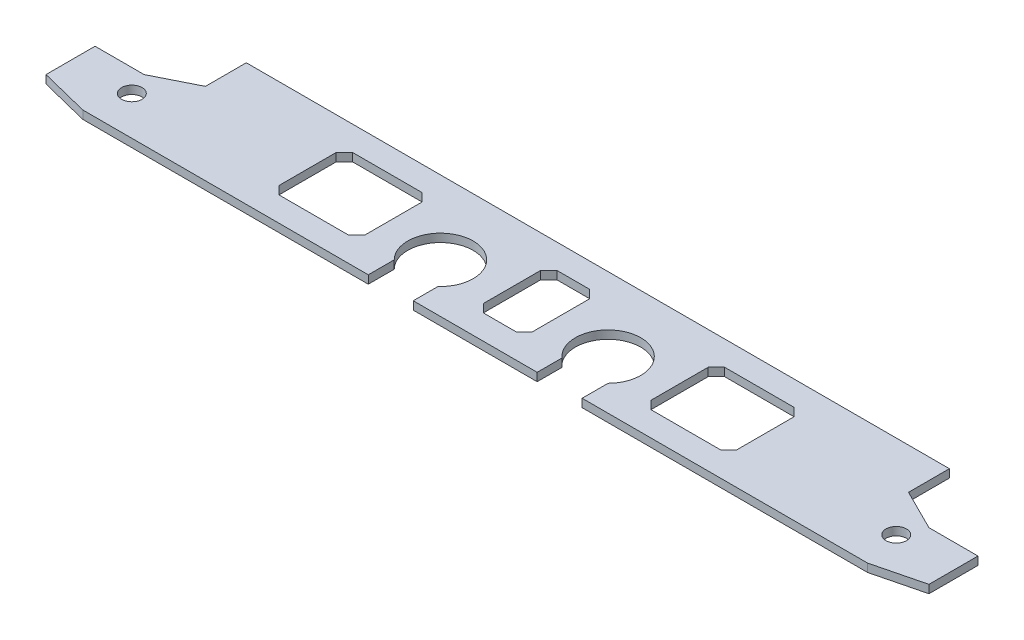
SolidWorks part; units mm, degrees
material "Thornel Mat VMA"
ref_plane "Alzado" through (0, 0, 0) normal (0, 0, 1) x (1, 0, 0)
ref_plane "Planta" through (0, 0, 0) normal (0, 1, 0) x (1, 0, 0)
ref_plane "Vista lateral" through (0, 0, 0) normal (1, 0, 0) x (0, 0, -1)
sketch "Croquis1" plane through (0, 0, 0) normal (0, 1, 0) x (1, 0, 0)
  line L1 (-43, 7.5) -> (43, 7.5)
  line L2 (-43, 7.5) -> (-43, -7.5)
  line L3 (-43, -7.5) -> (43, -7.5)
  line L4 (43, 7.5) -> (43, -7.5)
  line L5 (-43, 7.5) -> (43, -7.5) construction
  line L6 (-43, -7.5) -> (43, 7.5) construction
  point P0 (0, 0)
  dimension "D1" = 15
  dimension "D2" = 86
extrude "Saliente-Extruir1" add sketch "Croquis1" along normal blind 1
sketch "Croquis2" plane through (0, 1, 0) normal (0, 1, 0) x (1, 0, 0)
  line L0 (0, 7.5) -> (0, -7.5) construction
  line L1 (-3, 4.5) -> (3, 4.5)
  line L2 (-3, 4.5) -> (-3, -4.5)
  line L3 (-3, -4.5) -> (3, -4.5)
  line L4 (3, 4.5) -> (3, -4.5)
  line L5 (-3, 4.5) -> (3, -4.5) construction
  line L6 (-3, -4.5) -> (3, 4.5) construction
  line L7 (-43, -7.5) -> (43, -7.5) construction
  line L8 (43, -7.5) -> (43, 7.5) construction
  line L9 (17.5, 4.5) -> (28, 4.5)
  line L10 (17.5, 4.5) -> (17.5, -4.5)
  line L11 (17.5, -4.5) -> (28, -4.5)
  line L12 (28, 4.5) -> (28, -4.5)
  line L13 (17.5, 4.5) -> (28, -4.5) construction
  line L14 (17.5, -4.5) -> (28, 4.5) construction
  line L15 (-17.5, -4.5) -> (-28, -4.5)
  line L16 (-28, 4.5) -> (-28, -4.5)
  line L17 (-17.5, 4.5) -> (-28, 4.5)
  line L18 (-17.5, 4.5) -> (-17.5, -4.5)
  point P0 (0, 0)
  point P5 (22.75, 0)
  point P11 (0, 0)
  dimension "D1" = 9
  dimension "D2" = 6
  dimension "D3" = 9
  dimension "D4" = 10.5
  dimension "D5" = 15
extrude "Cortar-Extruir1" cut sketch "Croquis2" against normal blind 1
chamfer "Chaflán1" distance 1 12 edges at (17.5, 0.5, -4.5) (28, 0.5, -4.5) (3, 0.5, -4.5) (-3, 0.5, -4.5) (-3, 0.5, 4.5) (17.5, 0.5, 4.5) (28, 0.5, 4.5) (3, 0.5, 4.5) (-17.5, 0.5, 4.5) (-28, 0.5, 4.5) (-17.5, 0.5, -4.5) (-28, 0.5, -4.5)
sketch "Croquis3" plane through (0, 1, 0) normal (0, 1, 0) x (1, 0, 0)
  line L0 (0, 0) -> (0, -7.5) construction
  line L1 (-43, -7.5) -> (43, -7.5) construction
  line L2 (6.25, -1.5) -> (6.25, 2.5) construction
  line L3 (6.25, 2.5) -> (10.25, 2.5) construction
  line L4 (43, 7.5) -> (-43, 7.5) construction
  line L5 (3, -1.5) -> (17.5, -1.5) construction
  line L6 (3, -3.5) -> (3, 3.5) construction
  line L7 (17.5, 3.5) -> (17.5, -3.5) construction
  line L8 (-13.0785, -7.5) -> (-7.5785, -7.5)
  line L9 (7.5785, -7.5) -> (7.5785, -4.4771)
  line L11 (13.0785, -4.3283) -> (13.0785, -7.5)
  line L12 (13.0785, -7.5) -> (7.5785, -7.5)
  line L13 (-13.0785, -4.3283) -> (-13.0785, -7.5)
  line L14 (-7.5785, -7.5) -> (-7.5785, -4.4771)
  arc A0 (13.0785, -4.3283) -> (7.5785, -4.4771) centre (10.25, -1.5) ccw
  arc A1 (-13.0785, -4.3283) -> (-7.5785, -4.4771) centre (-10.25, -1.5) cw
  point P19 (10.25, -1.5)
  point P23 (10.25, -5.5)
  dimension "D1" = 8
  dimension "D2" = 5
extrude "Cortar-Extruir2" cut sketch "Croquis3" against normal blind 1
sketch "Croquis4" plane through (0, 1, 0) normal (0, 1, 0) x (1, 0, 0)
  line L1 (-2, -4.5) -> (2, -4.5) construction
  line L5 (43, 2.5) -> (48, 0)
  line L6 (43, -7.5) -> (43, 7.5) construction
  line L7 (48, 0) -> (54, 0)
  line L8 (54, 0) -> (54, -6)
  line L9 (54, -6) -> (48, -7.5)
  line L10 (48, -7.5) -> (43, -7.5)
  line L11 (43, 7.5) -> (-43, 7.5) construction
  line L12 (43, 2.5) -> (43, -7.5)
  line L13 (0, 0) -> (0, -4.5) construction
  line L14 (-43, 2.5) -> (-48, 0)
  line L15 (-48, 0) -> (-54, 0)
  line L16 (-54, 0) -> (-54, -6)
  line L17 (-54, -6) -> (-48, -7.5)
  line L18 (-48, -7.5) -> (-43, -7.5)
  line L19 (-43, 2.5) -> (-43, -7.5)
  circle A0 centre (46.75, -2.75) radius 1.25
  circle A1 centre (-46.75, -2.75) radius 1.25
  point P1 (46.75, -4)
  point P30 (48, -2.75)
  dimension "D2" = 2.5
  dimension "D1" = 3.5
  dimension "D3" = 6
  dimension "D4" = 5
  dimension "D5" = 5
  dimension "D6" = 6
  dimension "D7" = 54
extrude "Saliente-Extruir2" add sketch "Croquis4" against normal blind 1 separate body
combine bodies "Combinar1" operation type add bodies to combine 103 104 105
